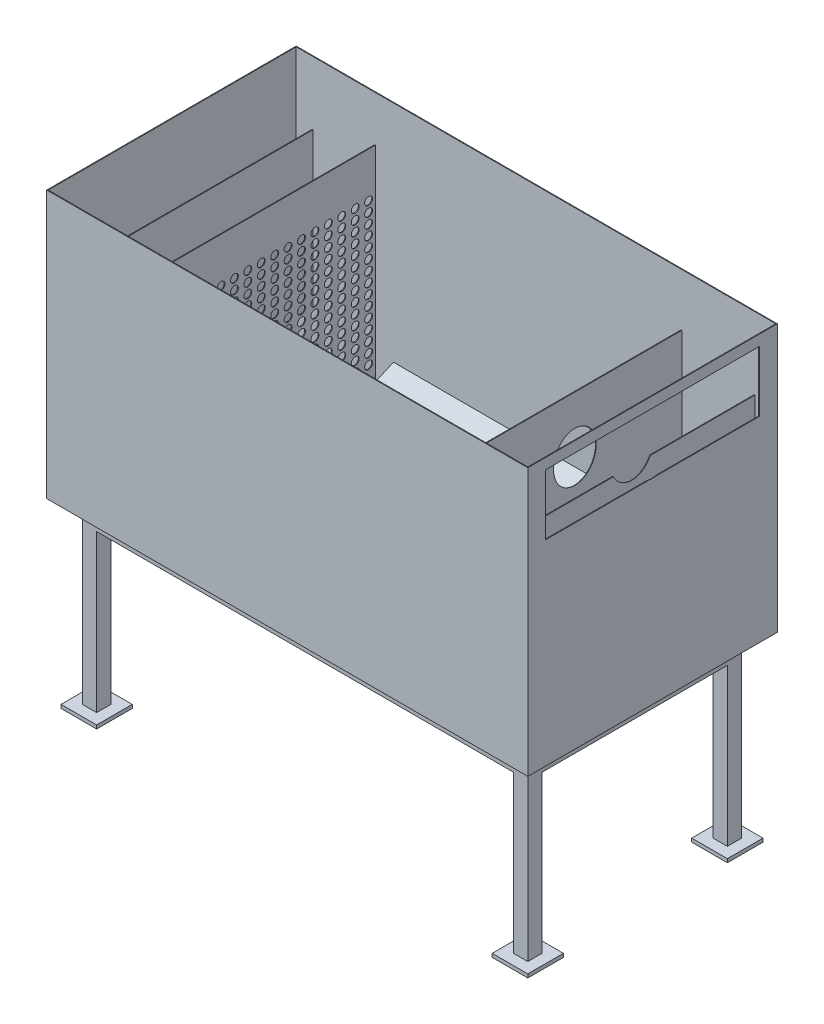
SolidWorks part; units mm, degrees
ref_plane "Спереди" through (0, 0, 0) normal (0, 0, 1) x (1, 0, 0)
ref_plane "Сверху" through (0, 0, 0) normal (0, 1, 0) x (1, 0, 0)
ref_plane "Справа" through (0, 0, 0) normal (1, 0, 0) x (0, 0, -1)
sketch "MASTER_FOOTPRINT" plane through (0, 0, 0) normal (0, 1, 0) x (1, 0, 0)
  line L1 (0, 0) -> (1350, 0)
  line L2 (0, 0) -> (0, 700)
  line L3 (0, 700) -> (1350, 700)
  line L4 (1350, 0) -> (1350, 700)
  dimension "D1" = 1350
  dimension "D2" = 700
extrude "BATH_BASE_PLATE" add sketch "MASTER_FOOTPRINT" along normal blind 750
shell "BATH_SHELL_2MM" thickness 2 removed face at (675, 750, -350)
sketch "Эскиз1" plane through (0, 0, 0) normal (1, 0, 0) x (0, 0, -1)
  circle A0 centre (350, 420) radius 50
extrude "INLET_D100_OPENING" cut sketch "Эскиз1" along normal blind 10
sketch "Эскиз2" plane through (0, 0, 0) normal (1, 0, 0) x (0, 0, -1)
  line L1 (80, 220) -> (620, 220)
  line L2 (80, 220) -> (80, 650)
  line L3 (80, 650) -> (620, 650)
  line L4 (620, 220) -> (620, 650)
extrude "INLET_IMPACT_BAFFLE" add sketch "Эскиз2" along normal blind 2 from offset 125 separate body
sketch "Эскиз3" plane through (0, 0, 0) normal (1, 0, 0) x (0, 0, -1)
  line L1 (30, 2) -> (670, 2)
  line L2 (30, 2) -> (30, 650)
  line L3 (30, 650) -> (670, 650)
  line L4 (670, 2) -> (670, 650)
  circle A0 centre (48.8235, 125) radius 11
  circle A1 centre (48.8235, 153.5) radius 11
  circle A2 centre (48.8235, 182) radius 11
  circle A3 centre (48.8235, 210.5) radius 11
  circle A4 centre (48.8235, 239) radius 11
  circle A5 centre (48.8235, 267.5) radius 11
  circle A6 centre (48.8235, 296) radius 11
  circle A7 centre (48.8235, 324.5) radius 11
  circle A8 centre (48.8235, 353) radius 11
  circle A9 centre (48.8235, 381.5) radius 11
  circle A10 centre (48.8235, 410) radius 11
  circle A11 centre (48.8235, 438.5) radius 11
  circle A12 centre (48.8235, 467) radius 11
  circle A13 centre (48.8235, 495.5) radius 11
  circle A14 centre (48.8235, 524) radius 11
  circle A15 centre (86.4706, 125) radius 11
  circle A16 centre (86.4706, 153.5) radius 11
  circle A17 centre (86.4706, 182) radius 11
  circle A18 centre (86.4706, 210.5) radius 11
  circle A19 centre (86.4706, 239) radius 11
  circle A20 centre (86.4706, 267.5) radius 11
  circle A21 centre (86.4706, 296) radius 11
  circle A22 centre (86.4706, 324.5) radius 11
  circle A23 centre (86.4706, 353) radius 11
  circle A24 centre (86.4706, 381.5) radius 11
  circle A25 centre (86.4706, 410) radius 11
  circle A26 centre (86.4706, 438.5) radius 11
  circle A27 centre (86.4706, 467) radius 11
  circle A28 centre (86.4706, 495.5) radius 11
  circle A29 centre (86.4706, 524) radius 11
  circle A30 centre (124.1176, 125) radius 11
  circle A31 centre (124.1176, 153.5) radius 11
  circle A32 centre (124.1176, 182) radius 11
  circle A33 centre (124.1176, 210.5) radius 11
  circle A34 centre (124.1176, 239) radius 11
  circle A35 centre (124.1176, 267.5) radius 11
  circle A36 centre (124.1176, 296) radius 11
  circle A37 centre (124.1176, 324.5) radius 11
  circle A38 centre (124.1176, 353) radius 11
  circle A39 centre (124.1176, 381.5) radius 11
  circle A40 centre (124.1176, 410) radius 11
  circle A41 centre (124.1176, 438.5) radius 11
  circle A42 centre (124.1176, 467) radius 11
  circle A43 centre (124.1176, 495.5) radius 11
  circle A44 centre (124.1176, 524) radius 11
  circle A45 centre (161.7647, 125) radius 11
  circle A46 centre (161.7647, 153.5) radius 11
  circle A47 centre (161.7647, 182) radius 11
  circle A48 centre (161.7647, 210.5) radius 11
  circle A49 centre (161.7647, 239) radius 11
  circle A50 centre (161.7647, 267.5) radius 11
  circle A51 centre (161.7647, 296) radius 11
  circle A52 centre (161.7647, 324.5) radius 11
  circle A53 centre (161.7647, 353) radius 11
  circle A54 centre (161.7647, 381.5) radius 11
  circle A55 centre (161.7647, 410) radius 11
  circle A56 centre (161.7647, 438.5) radius 11
  circle A57 centre (161.7647, 467) radius 11
  circle A58 centre (161.7647, 495.5) radius 11
  circle A59 centre (161.7647, 524) radius 11
  circle A60 centre (199.4118, 125) radius 11
  circle A61 centre (199.4118, 153.5) radius 11
  circle A62 centre (199.4118, 182) radius 11
  circle A63 centre (199.4118, 210.5) radius 11
  circle A64 centre (199.4118, 239) radius 11
  circle A65 centre (199.4118, 267.5) radius 11
  circle A66 centre (199.4118, 296) radius 11
  circle A67 centre (199.4118, 324.5) radius 11
  circle A68 centre (199.4118, 353) radius 11
  circle A69 centre (199.4118, 381.5) radius 11
  circle A70 centre (199.4118, 410) radius 11
  circle A71 centre (199.4118, 438.5) radius 11
  circle A72 centre (199.4118, 467) radius 11
  circle A73 centre (199.4118, 495.5) radius 11
  circle A74 centre (199.4118, 524) radius 11
  circle A75 centre (237.0588, 125) radius 11
  circle A76 centre (237.0588, 153.5) radius 11
  circle A77 centre (237.0588, 182) radius 11
  circle A78 centre (237.0588, 210.5) radius 11
  circle A79 centre (237.0588, 239) radius 11
  circle A80 centre (237.0588, 267.5) radius 11
  circle A81 centre (237.0588, 296) radius 11
  circle A82 centre (237.0588, 324.5) radius 11
  circle A83 centre (237.0588, 353) radius 11
  circle A84 centre (237.0588, 381.5) radius 11
  circle A85 centre (237.0588, 410) radius 11
  circle A86 centre (237.0588, 438.5) radius 11
  circle A87 centre (237.0588, 467) radius 11
  circle A88 centre (237.0588, 495.5) radius 11
  circle A89 centre (237.0588, 524) radius 11
  circle A90 centre (274.7059, 125) radius 11
  circle A91 centre (274.7059, 153.5) radius 11
  circle A92 centre (274.7059, 182) radius 11
  circle A93 centre (274.7059, 210.5) radius 11
  circle A94 centre (274.7059, 239) radius 11
  circle A95 centre (274.7059, 267.5) radius 11
  circle A96 centre (274.7059, 296) radius 11
  circle A97 centre (274.7059, 324.5) radius 11
  circle A98 centre (274.7059, 353) radius 11
  circle A99 centre (274.7059, 381.5) radius 11
  circle A100 centre (274.7059, 410) radius 11
  circle A101 centre (274.7059, 438.5) radius 11
  circle A102 centre (274.7059, 467) radius 11
  circle A103 centre (274.7059, 495.5) radius 11
  circle A104 centre (274.7059, 524) radius 11
  circle A105 centre (312.3529, 125) radius 11
  circle A106 centre (312.3529, 153.5) radius 11
  circle A107 centre (312.3529, 182) radius 11
  circle A108 centre (312.3529, 210.5) radius 11
  circle A109 centre (312.3529, 239) radius 11
  circle A110 centre (312.3529, 267.5) radius 11
  circle A111 centre (312.3529, 296) radius 11
  circle A112 centre (312.3529, 324.5) radius 11
  circle A113 centre (312.3529, 353) radius 11
  circle A114 centre (312.3529, 381.5) radius 11
  circle A115 centre (312.3529, 410) radius 11
  circle A116 centre (312.3529, 438.5) radius 11
  circle A117 centre (312.3529, 467) radius 11
  circle A118 centre (312.3529, 495.5) radius 11
  circle A119 centre (312.3529, 524) radius 11
  circle A120 centre (350, 125) radius 11
  circle A121 centre (350, 153.5) radius 11
  circle A122 centre (350, 182) radius 11
  circle A123 centre (350, 210.5) radius 11
  circle A124 centre (350, 239) radius 11
  circle A125 centre (350, 267.5) radius 11
  circle A126 centre (350, 296) radius 11
  circle A127 centre (350, 324.5) radius 11
  circle A128 centre (350, 353) radius 11
  circle A129 centre (350, 381.5) radius 11
  circle A130 centre (350, 410) radius 11
  circle A131 centre (350, 438.5) radius 11
  circle A132 centre (350, 467) radius 11
  circle A133 centre (350, 495.5) radius 11
  circle A134 centre (350, 524) radius 11
  circle A135 centre (387.6471, 125) radius 11
  circle A136 centre (387.6471, 153.5) radius 11
  circle A137 centre (387.6471, 182) radius 11
  circle A138 centre (387.6471, 210.5) radius 11
  circle A139 centre (387.6471, 239) radius 11
  circle A140 centre (387.6471, 267.5) radius 11
  circle A141 centre (387.6471, 296) radius 11
  circle A142 centre (387.6471, 324.5) radius 11
  circle A143 centre (387.6471, 353) radius 11
  circle A144 centre (387.6471, 381.5) radius 11
  circle A145 centre (387.6471, 410) radius 11
  circle A146 centre (387.6471, 438.5) radius 11
  circle A147 centre (387.6471, 467) radius 11
  circle A148 centre (387.6471, 495.5) radius 11
  circle A149 centre (387.6471, 524) radius 11
  circle A150 centre (425.2941, 125) radius 11
  circle A151 centre (425.2941, 153.5) radius 11
  circle A152 centre (425.2941, 182) radius 11
  circle A153 centre (425.2941, 210.5) radius 11
  circle A154 centre (425.2941, 239) radius 11
  circle A155 centre (425.2941, 267.5) radius 11
  circle A156 centre (425.2941, 296) radius 11
  circle A157 centre (425.2941, 324.5) radius 11
  circle A158 centre (425.2941, 353) radius 11
  circle A159 centre (425.2941, 381.5) radius 11
  circle A160 centre (425.2941, 410) radius 11
  circle A161 centre (425.2941, 438.5) radius 11
  circle A162 centre (425.2941, 467) radius 11
  circle A163 centre (425.2941, 495.5) radius 11
  circle A164 centre (425.2941, 524) radius 11
  circle A165 centre (462.9412, 125) radius 11
  circle A166 centre (462.9412, 153.5) radius 11
  circle A167 centre (462.9412, 182) radius 11
  circle A168 centre (462.9412, 210.5) radius 11
  circle A169 centre (462.9412, 239) radius 11
  circle A170 centre (462.9412, 267.5) radius 11
  circle A171 centre (462.9412, 296) radius 11
  circle A172 centre (462.9412, 324.5) radius 11
  circle A173 centre (462.9412, 353) radius 11
  circle A174 centre (462.9412, 381.5) radius 11
  circle A175 centre (462.9412, 410) radius 11
  circle A176 centre (462.9412, 438.5) radius 11
  circle A177 centre (462.9412, 467) radius 11
  circle A178 centre (462.9412, 495.5) radius 11
  circle A179 centre (462.9412, 524) radius 11
  circle A180 centre (500.5882, 125) radius 11
  circle A181 centre (500.5882, 153.5) radius 11
  circle A182 centre (500.5882, 182) radius 11
  circle A183 centre (500.5882, 210.5) radius 11
  circle A184 centre (500.5882, 239) radius 11
  circle A185 centre (500.5882, 267.5) radius 11
  circle A186 centre (500.5882, 296) radius 11
  circle A187 centre (500.5882, 324.5) radius 11
  circle A188 centre (500.5882, 353) radius 11
  circle A189 centre (500.5882, 381.5) radius 11
  circle A190 centre (500.5882, 410) radius 11
  circle A191 centre (500.5882, 438.5) radius 11
  circle A192 centre (500.5882, 467) radius 11
  circle A193 centre (500.5882, 495.5) radius 11
  circle A194 centre (500.5882, 524) radius 11
  circle A195 centre (538.2353, 125) radius 11
  circle A196 centre (538.2353, 153.5) radius 11
  circle A197 centre (538.2353, 182) radius 11
  circle A198 centre (538.2353, 210.5) radius 11
  circle A199 centre (538.2353, 239) radius 11
  circle A200 centre (538.2353, 267.5) radius 11
  circle A201 centre (538.2353, 296) radius 11
  circle A202 centre (538.2353, 324.5) radius 11
  circle A203 centre (538.2353, 353) radius 11
  circle A204 centre (538.2353, 381.5) radius 11
  circle A205 centre (538.2353, 410) radius 11
  circle A206 centre (538.2353, 438.5) radius 11
  circle A207 centre (538.2353, 467) radius 11
  circle A208 centre (538.2353, 495.5) radius 11
  circle A209 centre (538.2353, 524) radius 11
  circle A210 centre (575.8824, 125) radius 11
  circle A211 centre (575.8824, 153.5) radius 11
  circle A212 centre (575.8824, 182) radius 11
  circle A213 centre (575.8824, 210.5) radius 11
  circle A214 centre (575.8824, 239) radius 11
  circle A215 centre (575.8824, 267.5) radius 11
  circle A216 centre (575.8824, 296) radius 11
  circle A217 centre (575.8824, 324.5) radius 11
  circle A218 centre (575.8824, 353) radius 11
  circle A219 centre (575.8824, 381.5) radius 11
  circle A220 centre (575.8824, 410) radius 11
  circle A221 centre (575.8824, 438.5) radius 11
  circle A222 centre (575.8824, 467) radius 11
  circle A223 centre (575.8824, 495.5) radius 11
  circle A224 centre (575.8824, 524) radius 11
  circle A225 centre (613.5294, 125) radius 11
  circle A226 centre (613.5294, 153.5) radius 11
  circle A227 centre (613.5294, 182) radius 11
  circle A228 centre (613.5294, 210.5) radius 11
  circle A229 centre (613.5294, 239) radius 11
  circle A230 centre (613.5294, 267.5) radius 11
  circle A231 centre (613.5294, 296) radius 11
  circle A232 centre (613.5294, 324.5) radius 11
  circle A233 centre (613.5294, 353) radius 11
  circle A234 centre (613.5294, 381.5) radius 11
  circle A235 centre (613.5294, 410) radius 11
  circle A236 centre (613.5294, 438.5) radius 11
  circle A237 centre (613.5294, 467) radius 11
  circle A238 centre (613.5294, 495.5) radius 11
  circle A239 centre (613.5294, 524) radius 11
  circle A240 centre (651.1765, 125) radius 11
  circle A241 centre (651.1765, 153.5) radius 11
  circle A242 centre (651.1765, 182) radius 11
  circle A243 centre (651.1765, 210.5) radius 11
  circle A244 centre (651.1765, 239) radius 11
  circle A245 centre (651.1765, 267.5) radius 11
  circle A246 centre (651.1765, 296) radius 11
  circle A247 centre (651.1765, 324.5) radius 11
  circle A248 centre (651.1765, 353) radius 11
  circle A249 centre (651.1765, 381.5) radius 11
  circle A250 centre (651.1765, 410) radius 11
  circle A251 centre (651.1765, 438.5) radius 11
  circle A252 centre (651.1765, 467) radius 11
  circle A253 centre (651.1765, 495.5) radius 11
  circle A254 centre (651.1765, 524) radius 11
extrude "DISTRIBUTOR_D22" add sketch "Эскиз3" along normal blind 2 from offset 250 separate body
sketch "Эскиз4" plane through (0, 0, 0) normal (1, 0, 0) x (0, 0, -1)
  line L1 (50, 320) -> (650, 320)
  line L2 (50, 320) -> (50, 650)
  line L3 (50, 650) -> (650, 650)
  line L4 (650, 320) -> (650, 650)
extrude "OUTLET_SUBMERGED_BAFFLE" add sketch "Эскиз4" along normal blind 2 from offset 1130 separate body
sketch "Эскиз5" plane through (0, 0, 0) normal (1, 0, 0) x (0, 0, -1)
  line L1 (5, 2) -> (695, 2)
  line L2 (5, 2) -> (5, 550)
  line L3 (5, 550) -> (695, 550)
  line L4 (695, 2) -> (695, 550)
extrude "OVERFLOW_WEIR_Z550" add sketch "Эскиз5" along normal blind 2 from offset 1290 separate body
sketch "Эскиз6" plane through (0, 0, 0) normal (1, 0, 0) x (0, 0, -1)
  line L1 (50, 550) -> (650, 550)
  line L2 (50, 550) -> (50, 720)
  line L3 (50, 720) -> (650, 720)
  line L4 (650, 550) -> (650, 720)
extrude "OUTLET_WEIR_SLOT_W600" cut sketch "Эскиз6" along normal blind 10 from offset 1345
sketch "Эскиз7" plane through (0, 0, 0) normal (1, 0, 0) x (0, 0, -1)
  line L0 (2, -1) -> (2, 120)
  line L1 (2, 120) -> (280, -1)
  line L2 (280, -1) -> (2, -1)
  line L3 (698, -1) -> (698, 120)
  line L4 (698, 120) -> (420, -1)
  line L5 (420, -1) -> (698, -1)
extrude "SLOPED_SEDIMENT_FLOOR" add sketch "Эскиз7" along normal blind 825 from offset 275
sketch3d "SCREW_AXIS_30DEG_REFERENCE"
  line L0 (400, 70, -350) -> (1450, 676.2178, -350)
sketch "Эскиз8" plane through (0, 0, 0) normal (0, 1, 0) x (1, 0, 0)
  line L1 (50, 50) -> (90, 50)
  line L2 (50, 50) -> (50, 90)
  line L3 (50, 90) -> (90, 90)
  line L4 (90, 50) -> (90, 90)
  line L6 (50, 610) -> (90, 610)
  line L7 (50, 610) -> (50, 650)
  line L8 (50, 650) -> (90, 650)
  line L9 (90, 610) -> (90, 650)
  line L11 (1260, 50) -> (1300, 50)
  line L12 (1260, 50) -> (1260, 90)
  line L13 (1260, 90) -> (1300, 90)
  line L14 (1300, 50) -> (1300, 90)
  line L16 (1260, 610) -> (1300, 610)
  line L17 (1260, 610) -> (1260, 650)
  line L18 (1260, 650) -> (1300, 650)
  line L19 (1300, 610) -> (1300, 650)
extrude "FRAME_LEGS_40X40_H500" add sketch "Эскиз8" against normal blind 500
sketch "Эскиз9" plane through (0, 0, 0) normal (0, 1, 0) x (1, 0, 0)
  line L1 (50, 50) -> (1300, 50)
  line L2 (50, 50) -> (50, 90)
  line L3 (50, 90) -> (1300, 90)
  line L4 (1300, 50) -> (1300, 90)
  line L6 (50, 610) -> (1300, 610)
  line L7 (50, 610) -> (50, 650)
  line L8 (50, 650) -> (1300, 650)
  line L9 (1300, 610) -> (1300, 650)
extrude "FRAME_LONGITUDINAL_RAILS" add sketch "Эскиз9" against normal blind 40 from offset 20 offset against normal yes
sketch "Эскиз10" plane through (0, 0, 0) normal (0, 1, 0) x (1, 0, 0)
  line L1 (50, 90) -> (90, 90)
  line L2 (50, 90) -> (50, 610)
  line L3 (50, 610) -> (90, 610)
  line L4 (90, 90) -> (90, 610)
  line L6 (1260, 90) -> (1300, 90)
  line L7 (1260, 90) -> (1260, 610)
  line L8 (1260, 610) -> (1300, 610)
  line L9 (1300, 90) -> (1300, 610)
extrude "FRAME_TRANSVERSE_RAILS" add sketch "Эскиз10" against normal blind 40 from offset 20 offset against normal yes
sketch "Эскиз11" plane through (0, 0, 0) normal (0, 1, 0) x (1, 0, 0)
  line L1 (20, 20) -> (120, 20)
  line L2 (20, 20) -> (20, 120)
  line L3 (20, 120) -> (120, 120)
  line L4 (120, 20) -> (120, 120)
  line L6 (20, 580) -> (120, 580)
  line L7 (20, 580) -> (20, 680)
  line L8 (20, 680) -> (120, 680)
  line L9 (120, 580) -> (120, 680)
  line L11 (1230, 20) -> (1330, 20)
  line L12 (1230, 20) -> (1230, 120)
  line L13 (1230, 120) -> (1330, 120)
  line L14 (1330, 20) -> (1330, 120)
  line L16 (1230, 580) -> (1330, 580)
  line L17 (1230, 580) -> (1230, 680)
  line L18 (1230, 680) -> (1330, 680)
  line L19 (1330, 580) -> (1330, 680)
extrude "FRAME_FOOT_PADS_100X100" add sketch "Эскиз11" against normal blind 10 from offset 500 offset against normal yes
sweep "SEALED_SCREW_PASSAGE_D120" cut path "SCREW_AXIS_30DEG_REFERENCE" circular profile diameter 120 parameters "D3"=120
equation "\"AI_Q_Peak\"= 0.006"
equation "\"AI_B_Bath\"= 700"
equation "\"AI_L_Settle\"= 900"
equation "\"AI_L_Inlet\"= 250"
equation "\"AI_L_Outlet\"= 200"
equation "\"AI_L_Bath\"= 1350"
equation "\"AI_H_Water\"= 550"
equation "\"AI_H_Freeboard\"= 200"
equation "\"AI_H_Bath\"= 750"
equation "\"AI_Shell_Thickness\"= 2"
equation "\"AI_Inlet_DN\"= 100"
equation "\"AI_Weir_Width\"= 600"
equation "\"AI_Inlet_Baffle_Offset\"= 125"
equation "\"AI_Distributor_Open_Area\"= 0.28"
equation "\"AI_Distributor_Hole_Dia\"= 22"
equation "\"AI_Distributor_Blind_Zone\"= 110"
equation "\"AI_Outlet_Baffle_Depth\"= 250"
equation "\"AI_Screw_Diameter\"= 100"
equation "\"AI_Screw_Pitch\"= 100"
equation "\"AI_Screw_Angle\"= 30"
equation "\"AI_Screw_Rpm\"= 15"
equation "\"AI_Screw_Clearance\"= 5"
equation "\"AI_Liner_Thickness\"= 5"
equation "\"AI_Discharge_Height\"= 650"
equation "\"AI_Frame_Height\"= 500"
equation "\"D1@MASTER_FOOTPRINT\" = \"AI_L_Bath\""
equation "\"D2@MASTER_FOOTPRINT\" = \"AI_B_Bath\""
equation "\"D1@BATH_BASE_PLATE\" = \"AI_H_Bath\""
